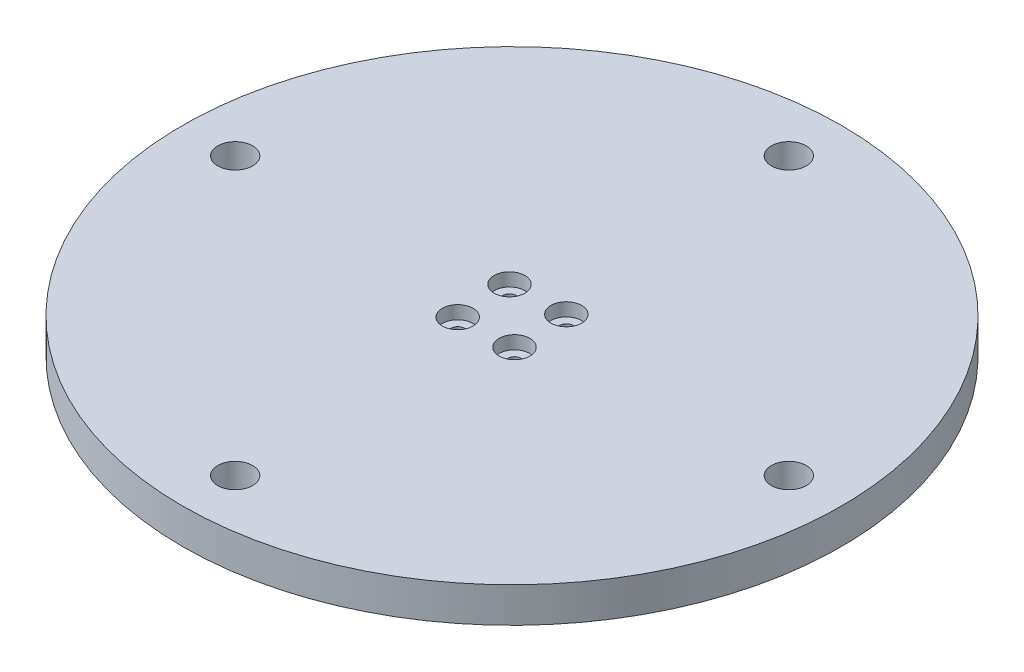
SolidWorks part; units mm, degrees
ref_plane "Alzado" through (0, 0, 0) normal (0, 0, 1) x (1, 0, 0)
ref_plane "Planta" through (0, 0, 0) normal (0, 1, 0) x (1, 0, 0)
ref_plane "Vista lateral" through (0, 0, 0) normal (1, 0, 0) x (0, 0, -1)
sketch "Croquis1" plane through (0, 0, 0) normal (0, 1, 0) x (1, 0, 0)
  circle A0 centre (0, 0) radius 15
extrude "Extruir-Lámina1" add sketch "Croquis1" along normal blind 18 thin thin type one direction reverse wall 2
sketch "Croquis2" plane through (0, 18, 0) normal (0, 1, 0) x (1, 0, 0)
  circle A0 centre (0, 0) radius 75
extrude "Saliente-Extruir1" add sketch "Croquis2" along normal blind 8
sketch "Croquis3" plane through (0, 26, 0) normal (0, 1, 0) x (1, 0, 0)
  line L0 (2.8872, -9.8739) -> (10.0969, -1.9704) construction
  circle A0 centre (5.8969, 6.4644) radius 1.59
  circle A1 centre (-5.8969, -6.4644) radius 1.59
  circle A2 centre (6.4921, -5.9222) radius 1.59
  circle A3 centre (-6.4644, 5.8969) radius 1.5875
  dimension "D1" = 3.175
  dimension "D2" = 3.18
  dimension "D3" = 3.18
  dimension "D4" = 3.18
extrude "Cortar-Extruir1" cut sketch "Croquis3" against normal blind 10
sketch "Croquis5" plane through (0, 18, 0) normal (0, -1, 0) x (1, 0, 0)
  line L0 (0, -75) -> (0, -63)
  circle A0 centre (0, 0) radius 75 construction
  circle A1 centre (0, -63) radius 3.969
  circle A2 centre (-63, 0) radius 3.969
  circle A3 centre (0, 63) radius 3.969
  circle A4 centre (63, 0) radius 3.969
  point P16 (0, 0)
  dimension "D1" = 7.938
  dimension "D2" = 4
extrude "Cortar-Extruir2" cut sketch "Croquis5" against normal blind 10 contours A1 | A2 | A3 | A4 region at (2.7271, 18, -65.7271) region at (-63, 18, 0)
sketch "Croquis6" plane through (0, 26, 0) normal (0, 1, 0) x (1, 0, 0)
  circle A0 centre (5.8969, 6.4644) radius 3.5
  circle A1 centre (-6.4644, 5.8969) radius 3.5
  circle A2 centre (-5.8969, -6.4644) radius 3.5
  circle A3 centre (6.4921, -5.9222) radius 3.5
extrude "Cortar-Extruir3" cut sketch "Croquis6" against normal blind 3
